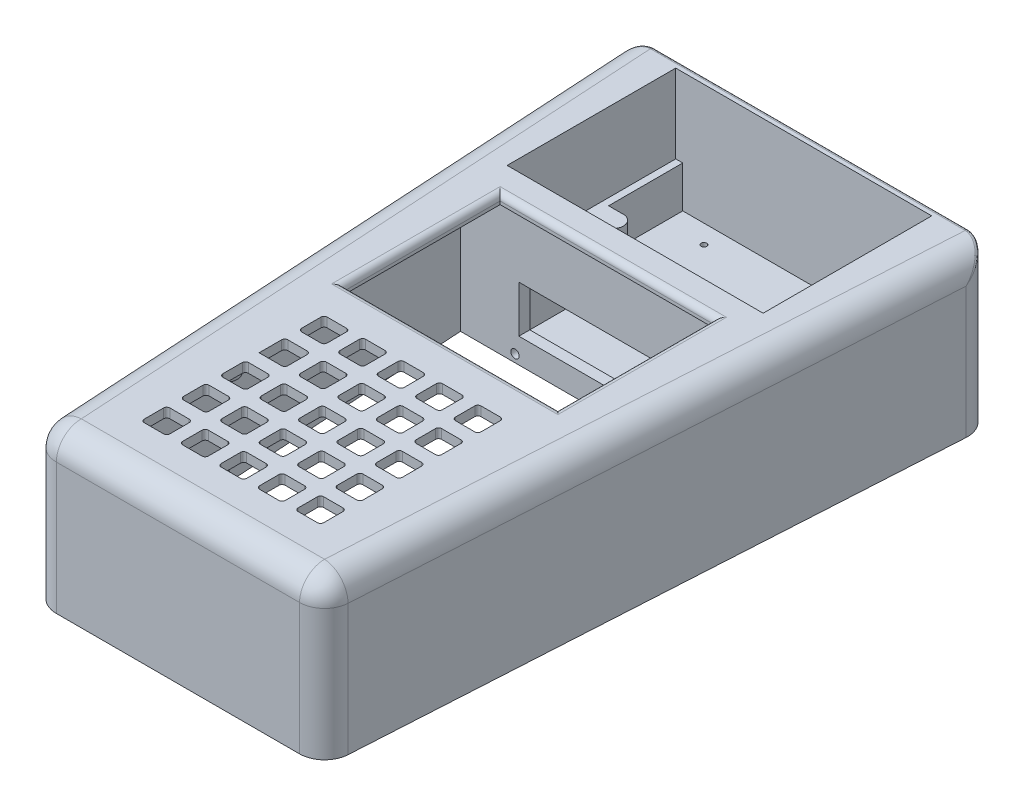
SolidWorks part; units mm, degrees
ref_plane "Front Plane" through (0, 0, 0) normal (0, 0, 1) x (1, 0, 0)
ref_plane "Top Plane" through (0, 0, 0) normal (0, 1, 0) x (1, 0, 0)
ref_plane "Right Plane" through (0, 0, 0) normal (1, 0, 0) x (0, 0, -1)
sketch "Sketch1" plane through (0, 0, 0) normal (0, 1, 0) x (1, 0, 0)
  line L8 (-46.5297, 101.5) -> (-58.5297, 101.5)
  line L9 (46.4703, 101.5) -> (-46.5297, 101.5)
  line L11 (46.5297, -101.5) -> (-46.4703, -101.5)
  line L15 (46.4703, 101.5) -> (-46.4703, -101.5) construction
  line L16 (46.5297, -101.5) -> (-46.5297, 101.5) construction
  line L17 (-58.5297, 101.5) -> (-46.4703, -101.5)
  line L18 (46.4703, 101.5) -> (58.4703, 101.5)
  line L19 (58.4703, 101.5) -> (46.5297, -101.5)
  point P0 (0, 0)
  dimension "D1" = 203
  dimension "D2" = 93
  dimension "D3" = 12
  dimension "D4" = 12
  dimension "D5" = 93
  dimension "D6" = 86.6
extrude "Boss-Extrude1" add sketch "Sketch1" along normal blind 50
sketch "Sketch2" plane through (0, 0, 0) normal (0, -1, 0) x (1, 0, 0)
  line L4 (52.4367, -41.5) -> (-52.4609, -41.5)
  line L8 (-44.1144, 99) -> (-55.8768, -99)
  line L9 (-55.8768, -99) -> (55.8189, -99)
  line L10 (55.8189, -99) -> (44.1724, 99)
  line L11 (44.1724, 99) -> (-44.1144, 99)
  line L12 (-44.1144, 99) -> (-52.4609, -41.5)
  line L14 (52.4367, -41.5) -> (44.1724, 99)
  line L15 (44.1724, 99) -> (-44.1144, 99)
  dimension "D2" = 140.5
  dimension "D1" = 2.5
extrude "Cut-Extrude1" cut sketch "Sketch2" against normal offset from surface (47 mm away) 3 up to face at (0, 50, 0)
sketch "Sketch3" plane through (0, 50, 0) normal (0, 1, 0) x (1, 0, 0)
  line L4 (-52.6689, 45) -> (52.6426, 45)
  line L8 (-55.8768, 99) -> (-44.1144, -99)
  line L9 (-44.1144, -99) -> (44.1724, -99)
  line L10 (44.1724, -99) -> (55.8189, 99)
  line L11 (55.8189, 99) -> (-55.8768, 99)
  line L12 (-55.8768, 99) -> (-52.6689, 45)
  line L14 (52.6426, 45) -> (55.8189, 99)
  line L15 (55.8189, 99) -> (-55.8768, 99)
  dimension "54" = 54
  dimension "D1" = 2.5
extrude "Cut-Extrude2" cut sketch "Sketch3" against normal offset from surface (47 mm away) 3 up to face at (0.0085, 0, 28.75)
sketch "Sketch4" plane through (0, 3, 0) normal (0, 1, 0) x (1, 0, 0)
  line L0 (55.8189, 99) -> (-55.8768, 99) construction
  line L1 (-38.7768, 99) -> (38.7232, 99) construction
  line L2 (-38.7768, 99) -> (-38.7768, 45) construction
  line L3 (-38.7768, 45) -> (38.7232, 45) construction
  line L4 (38.7232, 99) -> (38.7232, 45) construction
  line L5 (-52.6689, 45) -> (52.6426, 45) construction
  line L6 (-34.0268, 72) -> (-30.7768, 72) construction
  line L7 (-0.0268, 99) -> (-0.0268, 45) construction
  line L8 (38.7232, 68.75) -> (33.9732, 68.75)
  line L10 (-38.7768, 75.25) -> (-34.0268, 75.25)
  line L12 (-38.7768, 68.75) -> (-34.0268, 68.75)
  line L13 (-34.0268, 75.25) -> (-34.0268, 68.75) construction
  line L14 (38.7232, 75.25) -> (33.9732, 75.25)
  line L15 (-38.7768, 75.25) -> (-38.7768, 99)
  line L16 (-55.8768, 99) -> (-52.6689, 45) construction
  line L17 (-55.8768, 99) -> (-52.6689, 45)
  line L18 (52.6426, 45) -> (55.8189, 99) construction
  line L19 (52.6426, 45) -> (55.8189, 99)
  line L20 (-38.7768, 99) -> (-55.8768, 99)
  line L21 (-52.6689, 45) -> (-38.7768, 45)
  line L22 (-38.7768, 68.75) -> (-38.7768, 45)
  line L23 (38.7232, 75.25) -> (38.7232, 99)
  line L24 (38.7232, 99) -> (55.8189, 99)
  line L25 (38.7232, 68.75) -> (38.7232, 45)
  line L26 (38.7232, 45) -> (52.6426, 45)
  arc A0 (-34.0268, 68.75) -> (-34.0268, 75.25) centre (-34.0268, 72) ccw
  arc A1 (33.9732, 68.75) -> (33.9732, 75.25) centre (33.9732, 72) cw
  dimension "D1" = 77.5
  dimension "D2" = 17.1
  dimension "D3" = 6.5
  dimension "D5" = 23.75
extrude "Boss-Extrude2" add sketch "Sketch4" along normal offset from surface (21.8 mm away) 25.2 up to face at (-0.021, 50, -72)
sketch "Sketch5" plane through (0, 3, 0) normal (0, 1, 0) x (1, 0, 0)
  line L0 (-38.7768, 62.5) -> (28.7232, 62.5)
  line L1 (28.7232, 62.5) -> (28.7232, 45)
  line L10 (38.7232, 45) -> (38.7232, 68.75)
  line L11 (38.7232, 68.75) -> (33.9732, 68.75)
  line L12 (33.9732, 75.25) -> (38.7232, 75.25)
  line L13 (38.7232, 75.25) -> (38.7232, 99)
  line L14 (38.7232, 99) -> (-38.7768, 99)
  line L15 (-38.7768, 99) -> (-38.7768, 75.25)
  line L16 (-38.7768, 75.25) -> (-34.0268, 75.25)
  line L17 (-34.0268, 68.75) -> (-38.7768, 68.75)
  line L18 (-38.7768, 68.75) -> (-38.7768, 45)
  line L19 (-38.7768, 45) -> (38.7232, 45)
  line L20 (38.7232, 45) -> (38.7232, 68.75)
  line L21 (38.7232, 68.75) -> (33.9732, 68.75)
  line L22 (33.9732, 75.25) -> (38.7232, 75.25)
  line L23 (38.7232, 75.25) -> (38.7232, 99)
  line L24 (38.7232, 99) -> (-38.7768, 99)
  line L25 (-38.7768, 99) -> (-38.7768, 75.25)
  line L26 (-38.7768, 75.25) -> (-34.0268, 75.25)
  line L27 (-34.0268, 68.75) -> (-38.7768, 68.75)
  line L28 (-38.7768, 68.75) -> (-38.7768, 62.5)
  line L29 (28.7232, 45) -> (38.7232, 45)
  arc A2 (33.9732, 75.25) -> (33.9732, 68.75) centre (33.9732, 72) ccw
  arc A3 (-34.0268, 68.75) -> (-34.0268, 75.25) centre (-34.0268, 72) ccw
  arc A4 (33.9732, 75.25) -> (33.9732, 68.75) centre (33.9732, 72) ccw
  arc A5 (-34.0268, 68.75) -> (-34.0268, 75.25) centre (-34.0268, 72) ccw
  dimension "D2" = 17.5
  dimension "D3" = 10
  dimension "D1" = 0
extrude "Boss-Extrude3" add sketch "Sketch5" along normal offset from surface (8.5 mm away) 38.5 up to face at (-0.021, 50, -72)
sketch "Sketch6" plane through (0, 11.5, 0) normal (0, 1, 0) x (1, 0, 0)
  line L0 (-33.7768, 64) -> (30.2232, 64)
  line L1 (-33.7768, 96) -> (36.7232, 96)
  line L2 (-33.7768, 96) -> (-33.7768, 64)
  line L3 (30.2232, 50) -> (36.7232, 50)
  line L4 (36.7232, 96) -> (36.7232, 50)
  line L5 (30.2232, 64) -> (30.2232, 50)
  line L10 (28.7232, 45) -> (38.7232, 45)
  line L11 (38.7232, 45) -> (38.7232, 68.75)
  line L12 (38.7232, 68.75) -> (33.9732, 68.75)
  line L13 (33.9732, 75.25) -> (38.7232, 75.25)
  line L14 (38.7232, 75.25) -> (38.7232, 99)
  line L15 (38.7232, 99) -> (-38.7768, 99)
  line L16 (-38.7768, 99) -> (-38.7768, 75.25)
  line L17 (-38.7768, 75.25) -> (-34.0268, 75.25)
  line L18 (-34.0268, 68.75) -> (-38.7768, 68.75)
  line L19 (-38.7768, 68.75) -> (-38.7768, 62.5)
  line L20 (28.7232, 45) -> (38.7232, 45) construction
  line L21 (38.7232, 45) -> (38.7232, 68.75) construction
  line L22 (38.7232, 68.75) -> (33.9732, 68.75) construction
  line L23 (33.9732, 75.25) -> (38.7232, 75.25) construction
  line L24 (38.7232, 75.25) -> (38.7232, 99) construction
  line L25 (38.7232, 99) -> (-38.7768, 99) construction
  line L26 (-38.7768, 99) -> (-38.7768, 75.25) construction
  line L27 (-38.7768, 75.25) -> (-34.0268, 75.25) construction
  line L28 (-34.0268, 68.75) -> (-38.7768, 68.75) construction
  line L29 (-38.7768, 68.75) -> (-38.7768, 62.5) construction
  line L36 (-38.7768, 62.5) -> (28.7232, 62.5)
  line L37 (-38.7768, 62.5) -> (28.7232, 62.5) construction
  line L38 (28.7232, 62.5) -> (28.7232, 45)
  line L39 (28.7232, 62.5) -> (28.7232, 45) construction
  arc A2 (33.9732, 75.25) -> (33.9732, 68.75) centre (33.9732, 72) ccw
  arc A3 (-34.0268, 68.75) -> (-34.0268, 75.25) centre (-34.0268, 72) ccw
  arc A4 (33.9732, 75.25) -> (33.9732, 68.75) centre (33.9732, 72) ccw construction
  arc A5 (-34.0268, 68.75) -> (-34.0268, 75.25) centre (-34.0268, 72) ccw construction
  point P13 (-38.7768, 87.125)
  dimension "D2" = 5
  dimension "D3" = 3
  dimension "D4" = 2
  dimension "D5" = 5
  dimension "D6" = 1.5
  dimension "D7" = 1.5
  dimension "D1" = 0
extrude "Cut-Extrude3" cut sketch "Sketch6" along normal offset from surface (9.5 mm away) 2 from surface up to face at (4.0804, 11.5, -70.6429) starting at face at (0.0085, 0, 28.75)
sketch "Sketch7" plane through (0, 11.5, 0) normal (0, 1, 0) x (1, 0, 0)
  line L0 (-38.7768, 99) -> (-38.7768, 75.25) construction
  line L1 (38.7232, 99) -> (-38.7768, 99) construction
  line L2 (-38.7768, 68.75) -> (-38.7768, 45) construction
  line L4 (38.7232, 75.25) -> (38.7232, 99) construction
  line L5 (28.7232, 45) -> (38.7232, 45) construction
  line L6 (38.7232, 45) -> (38.7232, 68.75) construction
  circle A0 centre (-25.9768, 93) radius 0.9
  circle A1 centre (-27.6768, 68.1) radius 0.9
  circle A2 centre (25.9232, 93) radius 0.9
  circle A3 centre (34.5232, 58) radius 0.9
  dimension "D3" = 1.8
  dimension "D6" = 1.8
  dimension "D9" = 1.8
  dimension "D10" = 1.8
  dimension "D1" = 12.8
  dimension "D2" = 6
  dimension "D4" = 11.1
  dimension "D5" = 30.9
  dimension "D7" = 12.8
  dimension "D8" = 6
  dimension "D11" = 13
  dimension "D12" = 4.2
extrude "Cut-Extrude4" cut sketch "Sketch7" against normal up to next
sketch "Sketch9" plane through (0, 50, 0) normal (0, 1, 0) x (1, 0, 0)
  line L0 (-52.6689, 45) -> (52.6426, 45) construction
  line L1 (-34.2768, 36) -> (34.2232, 36)
  line L2 (-34.2768, 36) -> (-34.2768, -14)
  line L3 (-34.2768, -14) -> (34.2232, -14)
  line L4 (34.2232, 36) -> (34.2232, -14)
  line L5 (-34.2768, -14) -> (-34.2768, -101.5) construction
  line L6 (-46.4703, -101.5) -> (46.5297, -101.5) construction
  line L7 (-34.2768, -101.5) -> (34.2232, -101.5) construction
  line L8 (34.2232, -101.5) -> (34.2232, -14) construction
  line L9 (-28.7768, -25.9) -> (-28.7768, -84.5) construction
  line L10 (28.7232, -25.9) -> (28.7232, -84.5) construction
  line L11 (-28.7768, -25.9) -> (28.7232, -25.9) construction
  line L13 (-16.4568, -25.9) -> (-16.4568, -34.1)
  line L14 (-28.7768, -25.9) -> (-20.5768, -25.9)
  line L15 (-28.7768, -25.9) -> (-28.7768, -34.1)
  line L16 (-28.7768, -34.1) -> (-20.5768, -34.1)
  line L17 (-20.5768, -25.9) -> (-20.5768, -34.1)
  line L18 (-16.4568, -25.9) -> (-8.2568, -25.9)
  line L19 (-8.2568, -25.9) -> (-8.2568, -34.1)
  line L20 (-16.4568, -34.1) -> (-8.2568, -34.1)
  line L21 (-4.1368, -25.9) -> (-4.1368, -34.1)
  line L22 (-4.1368, -25.9) -> (4.0632, -25.9)
  line L23 (4.0632, -25.9) -> (4.0632, -34.1)
  line L24 (-4.1368, -34.1) -> (4.0632, -34.1)
  line L25 (8.1832, -25.9) -> (8.1832, -34.1)
  line L26 (8.1832, -25.9) -> (16.3832, -25.9)
  line L27 (16.3832, -25.9) -> (16.3832, -34.1)
  line L28 (8.1832, -34.1) -> (16.3832, -34.1)
  line L29 (20.5032, -25.9) -> (20.5032, -34.1)
  line L30 (20.5032, -25.9) -> (28.7032, -25.9)
  line L31 (28.7032, -25.9) -> (28.7032, -34.1)
  line L32 (20.5032, -34.1) -> (28.7032, -34.1)
  line L33 (-16.4568, -38.5) -> (-16.4568, -46.7)
  line L34 (-16.4568, -38.5) -> (-8.2568, -38.5)
  line L35 (-8.2568, -38.5) -> (-8.2568, -46.7)
  line L36 (-16.4568, -46.7) -> (-8.2568, -46.7)
  line L37 (-4.1368, -38.5) -> (-4.1368, -46.7)
  line L38 (-4.1368, -38.5) -> (4.0632, -38.5)
  line L39 (4.0632, -38.5) -> (4.0632, -46.7)
  line L40 (-4.1368, -46.7) -> (4.0632, -46.7)
  line L41 (8.1832, -38.5) -> (8.1832, -46.7)
  line L42 (8.1832, -38.5) -> (16.3832, -38.5)
  line L43 (16.3832, -38.5) -> (16.3832, -46.7)
  line L44 (8.1832, -46.7) -> (16.3832, -46.7)
  line L45 (20.5032, -38.5) -> (20.5032, -46.7)
  line L46 (20.5032, -38.5) -> (28.7032, -38.5)
  line L47 (28.7032, -38.5) -> (28.7032, -46.7)
  line L48 (20.5032, -46.7) -> (28.7032, -46.7)
  line L49 (-16.4568, -51.1) -> (-16.4568, -59.3)
  line L50 (-16.4568, -51.1) -> (-8.2568, -51.1)
  line L51 (-8.2568, -51.1) -> (-8.2568, -59.3)
  line L52 (-16.4568, -59.3) -> (-8.2568, -59.3)
  line L53 (-4.1368, -51.1) -> (-4.1368, -59.3)
  line L54 (-4.1368, -51.1) -> (4.0632, -51.1)
  line L55 (4.0632, -51.1) -> (4.0632, -59.3)
  line L56 (-4.1368, -59.3) -> (4.0632, -59.3)
  line L57 (8.1832, -51.1) -> (8.1832, -59.3)
  line L58 (8.1832, -51.1) -> (16.3832, -51.1)
  line L59 (16.3832, -51.1) -> (16.3832, -59.3)
  line L60 (8.1832, -59.3) -> (16.3832, -59.3)
  line L61 (20.5032, -51.1) -> (20.5032, -59.3)
  line L62 (20.5032, -51.1) -> (28.7032, -51.1)
  line L63 (28.7032, -51.1) -> (28.7032, -59.3)
  line L64 (20.5032, -59.3) -> (28.7032, -59.3)
  line L65 (-16.4568, -63.7) -> (-16.4568, -71.9)
  line L66 (-16.4568, -63.7) -> (-8.2568, -63.7)
  line L67 (-8.2568, -63.7) -> (-8.2568, -71.9)
  line L68 (-16.4568, -71.9) -> (-8.2568, -71.9)
  line L69 (-4.1368, -63.7) -> (-4.1368, -71.9)
  line L70 (-4.1368, -63.7) -> (4.0632, -63.7)
  line L71 (4.0632, -63.7) -> (4.0632, -71.9)
  line L72 (-4.1368, -71.9) -> (4.0632, -71.9)
  line L73 (8.1832, -63.7) -> (8.1832, -71.9)
  line L74 (8.1832, -63.7) -> (16.3832, -63.7)
  line L75 (16.3832, -63.7) -> (16.3832, -71.9)
  line L76 (8.1832, -71.9) -> (16.3832, -71.9)
  line L77 (20.5032, -63.7) -> (20.5032, -71.9)
  line L78 (20.5032, -63.7) -> (28.7032, -63.7)
  line L79 (28.7032, -63.7) -> (28.7032, -71.9)
  line L80 (20.5032, -71.9) -> (28.7032, -71.9)
  line L81 (-16.4568, -76.3) -> (-16.4568, -84.5)
  line L82 (-16.4568, -76.3) -> (-8.2568, -76.3)
  line L83 (-8.2568, -76.3) -> (-8.2568, -84.5)
  line L84 (-16.4568, -84.5) -> (-8.2568, -84.5)
  line L85 (-4.1368, -76.3) -> (-4.1368, -84.5)
  line L86 (-4.1368, -76.3) -> (4.0632, -76.3)
  line L87 (4.0632, -76.3) -> (4.0632, -84.5)
  line L88 (-4.1368, -84.5) -> (4.0632, -84.5)
  line L89 (8.1832, -76.3) -> (8.1832, -84.5)
  line L90 (8.1832, -76.3) -> (16.3832, -76.3)
  line L91 (16.3832, -76.3) -> (16.3832, -84.5)
  line L92 (8.1832, -84.5) -> (16.3832, -84.5)
  line L93 (20.5032, -76.3) -> (20.5032, -84.5)
  line L94 (20.5032, -76.3) -> (28.7032, -76.3)
  line L95 (28.7032, -76.3) -> (28.7032, -84.5)
  line L96 (20.5032, -84.5) -> (28.7032, -84.5)
  line L97 (-28.7768, -38.5) -> (-28.7768, -46.7)
  line L98 (-28.7768, -38.5) -> (-20.5768, -38.5)
  line L99 (-20.5768, -38.5) -> (-20.5768, -46.7)
  line L100 (-28.7768, -46.7) -> (-20.5768, -46.7)
  line L101 (-28.7768, -51.1) -> (-28.7768, -59.3)
  line L102 (-28.7768, -51.1) -> (-20.5768, -51.1)
  line L103 (-20.5768, -51.1) -> (-20.5768, -59.3)
  line L104 (-28.7768, -59.3) -> (-20.5768, -59.3)
  line L105 (-28.7768, -63.7) -> (-28.7768, -71.9)
  line L106 (-28.7768, -63.7) -> (-20.5768, -63.7)
  line L107 (-20.5768, -63.7) -> (-20.5768, -71.9)
  line L108 (-28.7768, -71.9) -> (-20.5768, -71.9)
  line L109 (-28.7768, -76.3) -> (-28.7768, -84.5)
  line L110 (-28.7768, -76.3) -> (-20.5768, -76.3)
  line L111 (-20.5768, -76.3) -> (-20.5768, -84.5)
  line L112 (-28.7768, -84.5) -> (-20.5768, -84.5)
  line L113 (-28.7768, -25.9) -> (-16.4568, -25.9) construction
  line L114 (-28.7768, -25.9) -> (-28.7768, -38.5) construction
  line L115 (55.8189, 99) -> (-55.8768, 99) construction
  dimension "D1" = 50
  dimension "D2" = 68.5
  dimension "D3" = 9
  dimension "D4" = 21.6
  dimension "D5" = 57.5
  dimension "D6" = 11.9
  dimension "D7" = 5.5
  dimension "D9" = 8.2
  dimension "D10" = 8.2
  dimension "D11" = 5
  dimension "D12" = 5
  dimension "D15" = 58.6
  dimension "D16" = 57.48
extrude "Cut-Extrude5" cut sketch "Sketch9" against normal up to next (3 mm away)
sketch "Sketch11" plane through (0, 47, 0) normal (0, -1, 0) x (1, 0, 0)
  line L0 (20.5032, 34.1) -> (28.7032, 34.1) construction
  line L1 (20.5032, 25.9) -> (20.5032, 34.1) construction
  line L2 (-28.7768, 34.1) -> (-20.5768, 34.1) construction
  line L5 (21.6032, 27) -> (21.6032, 33) construction
  line L6 (-28.7768, 46.7) -> (-20.5768, 46.7) construction
  line L7 (20.5032, 84.5) -> (28.7032, 84.5) construction
  line L8 (20.5032, 76.3) -> (20.5032, 84.5) construction
  line L9 (28.7032, 76.3) -> (20.5032, 76.3) construction
  line L10 (28.7032, 84.5) -> (28.7032, 76.3) construction
  line L11 (-20.5768, 38.5) -> (-28.7768, 38.5) construction
  line L12 (-28.7768, 38.5) -> (-28.7768, 46.7) construction
  line L13 (-20.5768, 46.7) -> (-20.5768, 38.5) construction
  line L14 (28.7032, 25.9) -> (20.5032, 25.9) construction
  line L15 (28.7032, 34.1) -> (28.7032, 25.9) construction
  line L16 (-28.7768, 25.9) -> (-28.7768, 34.1) construction
  line L17 (-20.5768, 25.9) -> (-28.7768, 25.9) construction
  line L18 (-20.5768, 34.1) -> (-20.5768, 25.9) construction
  line L19 (20.5032, 84.5) -> (28.7032, 84.5) construction
  line L20 (20.5032, 76.3) -> (20.5032, 84.5) construction
  line L21 (28.7032, 76.3) -> (20.5032, 76.3) construction
  line L22 (28.7032, 84.5) -> (28.7032, 76.3) construction
  line L23 (-20.5768, 38.5) -> (-28.7768, 38.5) construction
  line L24 (-28.7768, 38.5) -> (-28.7768, 46.7) construction
  line L25 (-20.5768, 46.7) -> (-20.5768, 38.5) construction
  line L26 (-28.7768, 46.7) -> (-20.5768, 46.7) construction
  line L27 (20.5032, 25.9) -> (20.5032, 34.1) construction
  line L28 (28.7032, 25.9) -> (20.5032, 25.9) construction
  line L29 (28.7032, 34.1) -> (28.7032, 25.9) construction
  line L30 (20.5032, 34.1) -> (28.7032, 34.1) construction
  line L31 (-28.7768, 34.1) -> (-20.5768, 34.1) construction
  line L32 (-28.7768, 25.9) -> (-28.7768, 34.1) construction
  line L33 (-20.5768, 25.9) -> (-28.7768, 25.9) construction
  line L34 (-20.5768, 34.1) -> (-20.5768, 25.9) construction
  line L35 (21.6032, 33) -> (27.6032, 33) construction
  line L36 (27.6032, 33) -> (27.6032, 27) construction
  line L37 (27.6032, 27) -> (21.6032, 27) construction
  line L38 (-27.6768, 33) -> (-21.6768, 33) construction
  line L39 (-21.6768, 33) -> (-21.6768, 27) construction
  line L40 (-21.6768, 27) -> (-27.6768, 27) construction
  line L41 (-27.6768, 27) -> (-27.6768, 33) construction
  line L42 (-21.6768, 39.6) -> (-27.6768, 39.6) construction
  line L43 (-27.6768, 39.6) -> (-27.6768, 45.6) construction
  line L44 (-27.6768, 45.6) -> (-21.6768, 45.6) construction
  line L45 (-21.6768, 45.6) -> (-21.6768, 39.6) construction
  line L46 (21.6032, 83.4) -> (27.6032, 83.4) construction
  line L47 (27.6032, 83.4) -> (27.6032, 77.4) construction
  line L48 (27.6032, 77.4) -> (21.6032, 77.4) construction
  line L49 (21.6032, 77.4) -> (21.6032, 83.4) construction
  circle A0 centre (34.3032, 20.3) radius 1.5
  circle A1 centre (-37.6768, 20.3) radius 1.5
  circle A2 centre (-35.6768, 50.6) radius 1.5
  circle A3 centre (34.6032, 84.5) radius 1.5
  circle A4 centre (34.3032, 20.3) radius 4.5
  circle A5 centre (34.6032, 84.5) radius 4.5
  circle A6 centre (-37.6768, 20.3) radius 4.5
  circle A7 centre (-35.6768, 50.6) radius 4.5
  dimension "D1" = 3
  dimension "D4" = 3
  dimension "D7" = 3
  dimension "D9" = 5
  dimension "D3" = 12.7
  dimension "D11" = 3
  dimension "D2" = 12.7
  dimension "D5" = 12.7
  dimension "D6" = 10
  dimension "D8" = 8
  dimension "D12" = 13
  dimension "D13" = 0
  dimension "D10" = 1.1
  dimension "D14" = 3
extrude "Boss-Extrude4" add sketch "Sketch11" along normal blind 4 draft 10 contours A4 | A5 | A6 | A7
extrude "Cut-Extrude6" cut sketch "Sketch11<3>" along normal blind 5.5 contours A1 | A2 | A0 | A3
sketch "Sketch11<3>" plane through (0, 47, 0) normal (0, -1, 0) x (1, 0, 0) same geometry as "Sketch11"
sketch "Sketch12" plane through (0, 24.8, 0) normal (0, 1, 0) x (1, 0, 0)
  line L0 (55.8189, 99) -> (52.6426, 45) construction
  line L1 (55.8189, 99) -> (52.6426, 45)
  line L2 (-52.6689, 45) -> (-55.8768, 99) construction
  line L3 (-52.6689, 45) -> (-55.8768, 99)
  line L4 (-55.8768, 99) -> (-41.0268, 99)
  line L5 (-55.8768, 99) -> (-38.7768, 99) construction
  line L6 (-41.0268, 99) -> (-41.0268, 45)
  line L7 (-41.0268, 45) -> (-52.6689, 45)
  line L8 (40.9732, 99) -> (55.8189, 99)
  line L9 (38.7232, 99) -> (55.8189, 99) construction
  line L10 (40.9732, 99) -> (40.9732, 45)
  line L11 (40.9732, 45) -> (52.6426, 45)
  dimension "D1" = 82
  dimension "D2" = 14.85
extrude "Boss-Extrude6" add sketch "Sketch12" along normal up to surface (25.2 mm away) up to face at (-0.0268, 50, -11)
fillet "Fillet2" radius 8 7 edges at (46.5297, 25, 101.5) (-46.4703, 25, 101.5) (58.4703, 25, -101.5) (-58.5297, 25, -101.5) (52.5, 50, 0) (0.0297, 50, 101.5) (-52.5, 50, 0)
sketch "Sketch13" plane through (0, 0, -41.5) normal (0, 0, 1) x (1, 0, 0)
  line L0 (-0.0121, 0) -> (-0.0121, 4.5) construction
  line L1 (-52.4609, 0) -> (52.4367, 0) construction
  line L2 (-30.0106, 4.5) -> (29.9864, 4.5) construction
  circle A0 centre (-35.0106, 2.5) radius 1.35
  circle A2 centre (34.9864, 2.5) radius 1.35
  dimension "D2" = 2.7
extrude "Cut-Extrude7" cut sketch "Sketch13" against normal up to surface (3.5 mm away) up to face at (5.7232, 22.82, -45)
sketch "Sketch14" plane through (-49.8198, 0, 2.9596) normal (0.9982, 0, -0.0593) x (-0.0593, 0, -0.9982)
  circle A0 centre (-35.5942, 2.5) radius 1.35
  dimension "D1" = 2.7
extrude "Cut-Extrude8" cut sketch "Sketch14" against normal blind 2
sketch "Sketch15" plane through (49.8233, 0, 2.9306) normal (-0.9983, 0, -0.0587) x (-0.0587, 0, 0.9983)
  line L1 (-44.5074, 47) -> (-44.5074, 0) construction
  line L2 (96.2354, 47) -> (-44.5074, 47) construction
  circle A0 centre (35.6118, 2.5) radius 1.35
  dimension "D1" = 2.7
  dimension "D2" = 80.1192
  dimension "D3" = 44.5
extrude "Cut-Extrude9" cut sketch "Sketch15" against normal blind 2
fillet "Fillet3" radius 8 2 edges at (44.1724, 23.5, 99) (-44.1144, 23.5, 99)
sketch "Sketch17" plane through (0, 0, 0) normal (0, -1, 0) x (1, 0, 0)
  line L0 (-44.5615, 91.4744) -> (-36.5755, 91)
  line L1 (-36.5755, 91) -> (-36.5755, 99)
  line L2 (44.6154, 91.4697) -> (36.6292, 91)
  line L3 (36.6292, 91) -> (36.6292, 99)
  arc A0 (44.6154, 91.4697) -> (36.6292, 99) centre (36.6292, 91) ccw construction
  arc A1 (-36.5755, 99) -> (-44.5615, 91.4744) centre (-36.5755, 91) ccw construction
  arc A2 (44.6154, 91.4697) -> (36.6292, 99) centre (36.6292, 91) ccw
  arc A3 (-36.5755, 99) -> (-44.5615, 91.4744) centre (-36.5755, 91) ccw
extrude "Boss-Extrude8" add sketch "Sketch17" against normal up to surface (47 mm away) up to face at (-35.6768, 47, 46.1)
fillet "Fillet4" radius 5 2 edges at (-36.5755, 23.5, 91) (36.6292, 23.5, 91)
sketch "Sketch18" plane through (0, 0, 0) normal (0, -1, 0) x (1, 0, 0)
  line L0 (41.9228, 91.3114) -> (44.6154, 91.4697) construction
  line L1 (36.6292, 99) -> (36.6292, 96.3027) construction
  line L2 (-44.5615, 91.4744) -> (-41.8721, 91.3146) construction
  line L3 (-36.5755, 96.3058) -> (-36.5755, 99) construction
  arc A0 (49.9859, -101.5) -> (57.9721, -93.0302) centre (49.9859, -93.5) ccw construction
  arc A1 (49.9859, -101.5) -> (57.9721, -93.0302) centre (49.9859, -93.5) ccw construction
  arc A2 (-58.0263, -93.0256) -> (-50.0404, -101.5) centre (-50.0404, -93.5) ccw construction
  arc A3 (-58.0263, -93.0256) -> (-50.0404, -101.5) centre (-50.0404, -93.5) ccw construction
  arc A4 (46.9726, 93.9697) -> (38.9864, 101.5) centre (38.9864, 93.5) ccw construction
  arc A5 (46.9726, 93.9697) -> (38.9864, 101.5) centre (38.9864, 93.5) ccw construction
  arc A6 (-38.9314, 101.5) -> (-46.9174, 93.9744) centre (-38.9314, 93.5) ccw construction
  arc A7 (-38.9314, 101.5) -> (-46.9174, 93.9744) centre (-38.9314, 93.5) ccw construction
  circle A8 centre (49.9859, -93.5) radius 1.5
  circle A9 centre (-50.0404, -93.5) radius 1.5
  circle A10 centre (40.6292, 95.2422) radius 1.5
  circle A11 centre (-40.5755, 95.2447) radius 1.5
  dimension "D1" = 3
  dimension "D2" = 3
  dimension "D3" = 3
  dimension "D4" = 3
  dimension "D5" = 4
  dimension "D6" = 4
  dimension "D7" = 4
  dimension "D8" = 4
extrude "Cut-Extrude10" cut sketch "Sketch18" against normal blind 8
fillet "Fillet5" radius 1 99 edges at (4.0632, 48.5, 59.3) (-4.1368, 48.5, 59.3) (16.3832, 48.5, 46.7) (8.1832, 48.5, 46.7) (-20.5768, 48.5, 46.7) (-20.5768, 48.5, 84.5) (-28.7768, 48.5, 84.5) (8.1832, 48.5, 63.7) (16.3832, 48.5, 63.7) (-4.1368, 48.5, 63.7) (4.0632, 48.5, 63.7) (-16.4568, 48.5, 63.7) (-8.2568, 48.5, 63.7) (-28.7768, 48.5, 63.7) (-20.5768, 48.5, 63.7) (-28.7768, 48.5, 51.1) (-20.5768, 48.5, 51.1) (-16.4568, 48.5, 51.1) (-8.2568, 48.5, 51.1) (-4.1368, 48.5, 51.1) (4.0632, 48.5, 51.1) (8.1832, 48.5, 51.1) (16.3832, 48.5, 51.1) (8.1832, 48.5, 38.5) (16.3832, 48.5, 38.5) (-4.1368, 48.5, 38.5) (4.0632, 48.5, 38.5) (-16.4568, 48.5, 38.5) (-8.2568, 48.5, 38.5) (-28.7768, 48.5, 38.5) (-20.5768, 48.5, 38.5) (-16.4568, 48.5, 25.9) (-8.2568, 48.5, 25.9) (-28.7768, 48.5, 25.9) (-20.5768, 48.5, 25.9) (4.0632, 48.5, 25.9) (4.0632, 48.5, 34.1) (16.3832, 48.5, 25.9) (16.3832, 48.5, 34.1) (28.7032, 48.5, 25.9) (28.7032, 48.5, 34.1) (16.3832, 48.5, 59.3) (8.1832, 48.5, 59.3) (28.7032, 48.5, 59.3) (20.5032, 48.5, 59.3) (4.0632, 48.5, 46.7) (-4.1368, 48.5, 46.7) (-8.2568, 48.5, 59.3) (-16.4568, 48.5, 59.3) (-8.2568, 48.5, 46.7) (-16.4568, 48.5, 46.7) (-8.2568, 48.5, 34.1) (-16.4568, 48.5, 34.1) (-20.5768, 48.5, 34.1) (-28.7768, 48.5, 34.1) (-20.5768, 48.5, 59.3) (-28.7768, 48.5, 59.3) (-20.5768, 48.5, 71.9) (-28.7768, 48.5, 71.9) (-8.2568, 48.5, 71.9) (-16.4568, 48.5, 71.9) (4.0632, 48.5, 71.9) (-4.1368, 48.5, 71.9) (28.7032, 48.5, 71.9) (20.5032, 48.5, 71.9) (16.3832, 48.5, 71.9) (8.1832, 48.5, 71.9) (-8.2568, 48.5, 84.5) (-16.4568, 48.5, 84.5) (4.0632, 48.5, 84.5) (-4.1368, 48.5, 84.5) (16.3832, 48.5, 84.5) (8.1832, 48.5, 84.5) (28.7032, 48.5, 84.5) (20.5032, 48.5, 84.5) (20.5032, 48.5, 63.7) (28.7032, 48.5, 63.7) (20.5032, 48.5, 46.7) (20.5032, 48.5, 38.5) (20.5032, 48.5, 51.1) (28.7032, 48.5, 51.1) (28.7032, 48.5, 38.5) (28.7032, 48.5, 46.7) (-4.1368, 48.5, 76.3) (-16.4568, 48.5, 76.3) (-28.7768, 48.5, 76.3) (-4.1368, 48.5, 25.9) (8.1832, 48.5, 34.1) (8.1832, 48.5, 25.9) (20.5032, 48.5, 25.9) (20.5032, 48.5, 34.1) (-8.2568, 48.5, 76.3) (4.0632, 48.5, 76.3) (16.3832, 48.5, 76.3) (28.7032, 48.5, 76.3) (-20.5768, 48.5, 76.3) (-4.1368, 48.5, 34.1) (20.5032, 48.5, 76.3) (8.1832, 48.5, 76.3)
fillet "Fillet6" radius 2 4 edges at (-34.2768, 50, -11) (-0.0268, 50, 14) (34.2232, 50, -11) (-0.0268, 50, -36)
fillet "Fillet7" radius 1.2 5 edges at (55.9652, 47.6569, -98.8149) (50.2209, 50, -101.4965) (-56.0227, 47.6569, -98.8114) (-50.2777, 50, -101.4965) (-0.0272, 50, -101.5)
sketch "Sketch19" plane through (0, 0, -45) normal (0, 0, -1) x (-1, 0, 0)
  line L22 (31.8369, 8) -> (33.7768, 8)
  line L23 (33.7768, 8) -> (33.7768, 8.729)
  line L25 (-33.7232, 23) -> (33.7768, 23)
  line L26 (41.0268, 50) -> (-40.9732, 50) construction
  line L33 (-23.7232, 8) -> (31.8369, 8)
  line L34 (33.7768, 8.729) -> (33.7768, 29.8)
  line L35 (33.7768, 29.8) -> (36.0268, 29.8)
  line L36 (36.0268, 29.8) -> (36.0268, 45)
  line L37 (36.0268, 45) -> (-35.9732, 45)
  line L38 (-35.9732, 45) -> (-35.9732, 29.8)
  line L39 (-35.9732, 29.8) -> (-33.7232, 29.8)
  line L40 (-33.7232, 29.8) -> (-33.7232, 16.5)
  line L41 (-33.7232, 16.5) -> (-23.7232, 16.5)
  line L42 (-23.7232, 16.5) -> (-23.7232, 8)
  line L43 (-23.7232, 8) -> (31.8369, 8)
  line L44 (33.7768, 8.729) -> (33.7768, 23)
  line L50 (-33.7232, 23) -> (-33.7232, 16.5)
  line L51 (-33.7232, 16.5) -> (-23.7232, 16.5)
  line L52 (-23.7232, 16.5) -> (-23.7232, 8)
  arc A3 (33.7768, 8.729) -> (31.8369, 8) centre (35.0106, 2.5) ccw
  dimension "D2" = 27
  dimension "D1" = 5
extrude "Cut-Extrude11" cut sketch "Sketch19" against normal up to next
